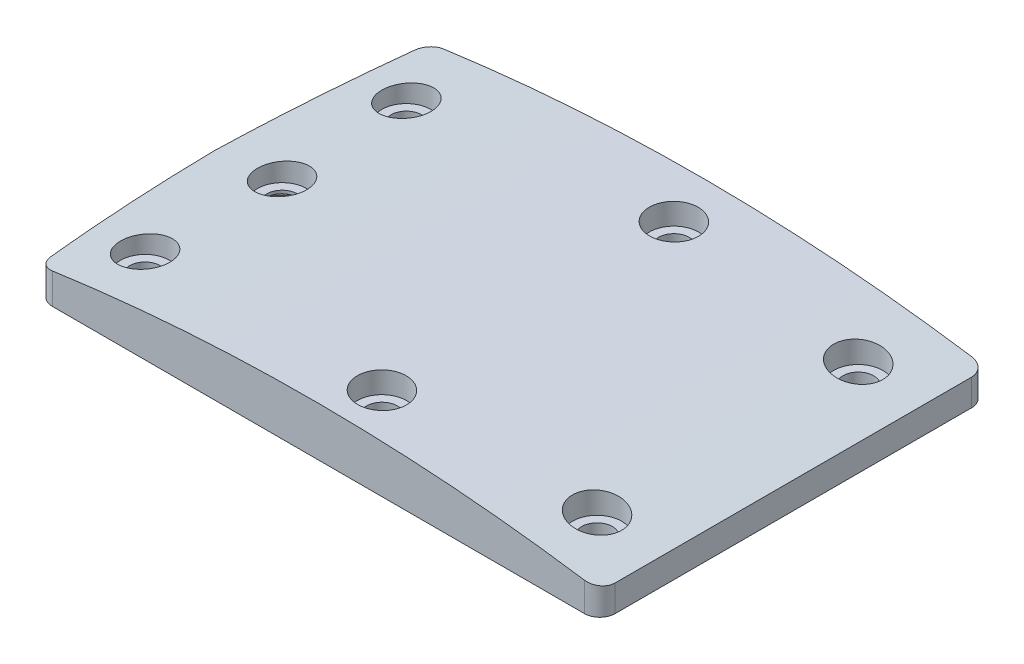
SolidWorks part; units mm, degrees
ref_plane "Front Plane" through (0, 0, 0) normal (0, 0, 1) x (1, 0, 0)
ref_plane "Top Plane" through (0, 0, 0) normal (0, 1, 0) x (1, 0, 0)
ref_plane "Right Plane" through (0, 0, 0) normal (1, 0, 0) x (0, 0, -1)
sketch "Sketch1" plane through (0, 0, 0) normal (0, 1, 0) x (1, 0, 0)
  line L1 (88.5752, 64.4067) -> (-83.4596, 64.4067)
  line L2 (93.5752, 59.4067) -> (93.5752, -56.5933)
  line L3 (88.5752, -61.5933) -> (-84.5844, -61.5933)
  line L5 (-76.4248, 0) -> (-76.3624, 0)
  line L13 (75.5752, -26.0764) -> (75.5752, 26.0764)
  line L14 (10.5752, 59.849) -> (10.5752, 49.4067) construction
  line L28 (-93.4248, 0) -> (-76.3624, 0)
  line L34 (147.9305, 0) -> (75.5752, 0) construction
  line L58 (28.2672, 49.4067) -> (54.5817, 49.4067)
  line L65 (75.5752, 48.9893) -> (75.5752, 49.4067)
  line L67 (75.5752, 64.4067) -> (75.5752, 77.8192)
  line L71 (10.5752, 44.4067) -> (10.5752, 38.9644) construction
  line L72 (-53.0672, 49.4067) -> (-6.3739, 49.4067)
  line L73 (-75.0534, 21.8192) -> (-75.0534, 17.3205)
  line L74 (10.5752, 44.4067) -> (10.5752, 38.9644) construction
  line L79 (-75.0534, -21.8192) -> (-75.0534, -17.3205)
  line L81 (-44.4248, 49.4067) -> (-44.4248, -49.4067)
  line L83 (-38.4248, 49.4067) -> (-38.4248, -49.4067)
  line L85 (-4.4248, -49.2149) -> (-4.4248, 49.2149)
  line L87 (1.5752, -45.474) -> (1.5752, 45.474)
  line L89 (35.5752, 49.4067) -> (35.5752, -49.4067)
  line L91 (41.5752, 49.4067) -> (41.5752, -49.4067)
  line L92 (-53.0672, -49.4067) -> (-6.3739, -49.4067)
  line L93 (28.2672, -49.4067) -> (54.5817, -49.4067)
  line L94 (-76.3624, 0) -> (-180.2852, 0) construction
  circle A0 centre (73.5752, 44.4067) radius 5
  circle A2 centre (-73.4248, 40.1495) radius 5
  circle A6 centre (10.5752, 49.4067) radius 5
  circle A27 centre (-71.4248, 0) radius 5
  arc A34 (-80.0534, 8.6603) -> (-80.0534, -8.6603) centre (-75.0534, 0) ccw
  arc A36 (-70.5181, 30.194) -> (-75.0534, 21.8192) centre (-65.0534, 21.8192) ccw
  arc A37 (-93.4248, 0) -> (-88.4151, 60.0719) centre (506.5049, -19.7858) cw
  arc A38 (-83.4596, 64.4067) -> (-88.4151, 60.0719) centre (-83.4596, 59.4067) ccw
  arc A39 (-93.4248, 0) -> (-89.5491, -57.1866) centre (465.7631, 9.1733) ccw
  arc A40 (-84.5844, -61.5933) -> (-89.5491, -57.1866) centre (-84.5844, -56.5933) cw
  arc A41 (88.5752, -61.5933) -> (93.5752, -56.5933) centre (88.5752, -56.5933) ccw
  arc A42 (93.5752, 59.4067) -> (88.5752, 64.4067) centre (88.5752, 59.4067) ccw
  arc A44 (-53.0672, 49.4067) -> (-63.0603, 39.7781) centre (-53.0672, 39.4067) ccw
  arc A45 (3.2464, 42.1362) -> (-6.3739, 49.4067) centre (-6.3739, 39.4067) ccw
  arc A46 (28.2672, 49.4067) -> (19.6069, 44.4067) centre (28.2672, 39.4067) ccw
  arc A47 (75.5752, 26.0764) -> (69.8802, 35.1023) centre (65.5752, 26.0764) ccw
  arc A49 (64.5609, 40.0516) -> (54.5817, 49.4067) centre (54.5817, 39.4067) ccw
  arc A50 (64.5609, 40.0516) -> (69.8802, 35.1023) centre (73.5752, 44.4067) ccw
  arc A51 (3.2464, 42.1362) -> (19.6069, 44.4067) centre (10.5752, 49.4067) ccw
  arc A52 (-70.5181, 30.194) -> (-63.0603, 39.7781) centre (-73.4248, 40.1495) ccw
  arc A53 (-80.0534, 8.6603) -> (-75.0534, 17.3205) centre (-85.0534, 17.3205) ccw
  circle A54 centre (73.5752, -44.4067) radius 5
  circle A55 centre (10.5752, -49.4067) radius 5
  circle A56 centre (-73.4248, -40.1495) radius 5
  arc A57 (-80.0534, -8.6603) -> (-80.0534, 8.6603) centre (-75.0534, 0) cw
  arc A58 (-80.0534, -8.6603) -> (-75.0534, -17.3205) centre (-85.0534, -17.3205) cw
  arc A59 (-70.5181, -30.194) -> (-75.0534, -21.8192) centre (-65.0534, -21.8192) cw
  arc A60 (-70.5181, -30.194) -> (-63.0603, -39.7781) centre (-73.4248, -40.1495) cw
  arc A61 (-53.0672, -49.4067) -> (-63.0603, -39.7781) centre (-53.0672, -39.4067) cw
  arc A62 (3.2464, -42.1362) -> (-6.3739, -49.4067) centre (-6.3739, -39.4067) cw
  arc A63 (3.2464, -42.1362) -> (19.6069, -44.4067) centre (10.5752, -49.4067) cw
  arc A64 (28.2672, -49.4067) -> (19.6069, -44.4067) centre (28.2672, -39.4067) cw
  arc A65 (64.5609, -40.0516) -> (54.5817, -49.4067) centre (54.5817, -39.4067) cw
  arc A66 (64.5609, -40.0516) -> (69.8802, -35.1023) centre (73.5752, -44.4067) cw
  arc A67 (75.5752, -26.0764) -> (69.8802, -35.1023) centre (65.5752, -26.0764) cw
  point P13 (-93.4248, 0)
  point P16 (0, 0)
  point P18 (0, 0)
  point P22 (0, 0)
  point P23 (0, 0)
  point P30 (0, 0)
  point P53 (93.5752, -61.5933)
  point P64 (93.5752, 64.4067)
  point P95 (41.5752, 0)
  point P96 (35.5752, 0)
  point P97 (1.5752, 0)
  point P98 (-4.4248, 0)
  point P99 (-38.4248, 0)
  point P100 (-44.4248, 0)
  dimension "D6" = 84
  dimension "D7" = 10
  dimension "D11" = 20
  dimension "D15" = 10
  dimension "D3" = 18
  dimension "10" = 10
  dimension "D26" = 22
  dimension "D29" = 187
  dimension "D16" = 10
  dimension "D2" = 126
  dimension "D4" = 65
  dimension "D9" = 15
  dimension "D18" = 20
sketch "Sketch4" plane through (0, 0, 0) normal (0, 1, 0) x (1, 0, 0)
  line L3 (88.5752, 64.4067) -> (-83.4596, 64.4067)
  line L4 (93.5752, -56.5933) -> (93.5752, 59.4067)
  line L5 (-84.5844, -61.5933) -> (88.5752, -61.5933)
  line L6 (88.5752, 64.4067) -> (-83.4596, 64.4067)
  line L7 (93.5752, -56.5933) -> (93.5752, 59.4067)
  line L8 (-84.5844, -61.5933) -> (88.5752, -61.5933)
  arc A14 (-88.4151, 60.0719) -> (-93.4248, 0) centre (506.5049, -19.7858) ccw
  arc A15 (-83.4596, 64.4067) -> (-88.4151, 60.0719) centre (-83.4596, 59.4067) ccw
  arc A16 (93.5752, 59.4067) -> (88.5752, 64.4067) centre (88.5752, 59.4067) ccw
  arc A17 (88.5752, -61.5933) -> (93.5752, -56.5933) centre (88.5752, -56.5933) ccw
  arc A18 (-89.5491, -57.1866) -> (-84.5844, -61.5933) centre (-84.5844, -56.5933) ccw
  arc A19 (-93.4248, 0) -> (-89.5491, -57.1866) centre (465.7631, 9.1733) ccw
  arc A20 (-88.4151, 60.0719) -> (-93.4248, 0) centre (506.5049, -19.7858) ccw
  arc A21 (-83.4596, 64.4067) -> (-88.4151, 60.0719) centre (-83.4596, 59.4067) ccw
  arc A22 (93.5752, 59.4067) -> (88.5752, 64.4067) centre (88.5752, 59.4067) ccw
  arc A23 (88.5752, -61.5933) -> (93.5752, -56.5933) centre (88.5752, -56.5933) ccw
  arc A24 (-89.5491, -57.1866) -> (-84.5844, -61.5933) centre (-84.5844, -56.5933) ccw
  arc A25 (-93.4248, 0) -> (-89.5491, -57.1866) centre (465.7631, 9.1733) ccw
  dimension "D5" = 0
extrude "Boss-Extrude1" add sketch "Sketch4" along normal blind 16
sketch "Sketch5" plane through (0, 0, 0) normal (0, 1, 0) x (1, 0, 0)
  line L0 (-93.4248, 0) -> (108.0865, 0) construction
  circle A0 centre (73.5752, -42.5) radius 5
  circle A1 centre (73.5752, 42.5) radius 5
  circle A3 centre (8.5752, -47.5) radius 5
  circle A5 centre (8.5752, 47.5) radius 5
  circle A7 centre (-73.4848, 42.515) radius 5
  circle A9 centre (-73.4848, -42.515) radius 5
  circle A11 centre (-71.4248, 0) radius 5
  dimension "D2" = 82.06
  dimension "D1" = 65
  dimension "D3" = 19.94
  dimension "D4" = 42.515
  dimension "D5" = 47.5
  dimension "D6" = 42.5
extrude "Cut-Extrude4" cut sketch "Sketch5" along normal through all from offset 16 offset against normal yes
sketch "Sketch7" plane through (0, 0, 0) normal (0, -1, 0) x (1, 0, 0)
  line L1 (-38.4248, 46.5933) -> (-5.7811, 46.5933)
  line L3 (24.9315, 46.5933) -> (35.5752, 46.5933)
  line L5 (41.5752, 46.5933) -> (56.1646, 46.5933)
  line L6 (75.5752, 26.5461) -> (75.5752, -26.5461)
  line L8 (-54.7435, 46.5933) -> (-44.4248, 46.5933)
  line L9 (-75.9293, 22.2) -> (-75.4248, 14.2829)
  line L12 (-44.4248, 46.5933) -> (-44.4248, -46.5933)
  line L14 (-38.4248, 46.5933) -> (-38.4248, -46.5933)
  line L16 (1.6129, 43.3959) -> (1.6129, -43.3259)
  line L18 (-4.4172, 46.62) -> (-4.4172, -46.5009)
  line L20 (41.5752, 46.5933) -> (41.5752, -46.5933)
  line L22 (35.5752, 46.5933) -> (35.5752, -46.5933)
  line L24 (41.5752, -46.5933) -> (56.1646, -46.5933)
  line L25 (24.9315, -46.5933) -> (35.5752, -46.5933)
  line L26 (-38.4248, -46.5933) -> (-5.7811, -46.5943)
  line L27 (-54.7435, -46.5933) -> (-44.4248, -46.5933)
  line L28 (-75.4248, -22.2889) -> (-75.4248, -14.2829)
  arc A0 (-69.7829, 33.2254) -> (-64.419, 38.2945) centre (-73.4848, 42.515) ccw
  arc A1 (-78.4248, 7.1414) -> (-78.4248, -7.1414) centre (-71.4248, 0) ccw
  arc A2 (1.8971, 43) -> (15.7241, 43.793) centre (8.5752, 47.5) ccw
  arc A4 (-54.7435, 46.5933) -> (-64.419, 38.2945) centre (-50.4409, 31.7872) ccw
  arc A5 (1.8971, 43) -> (1.6129, 43.3959) centre (-4.9383, 38.394) ccw
  arc A6 (24.9315, 46.5933) -> (15.7241, 43.793) centre (21.6953, 40.6967) ccw
  arc A7 (65.3699, 40.5) -> (56.1646, 46.5933) centre (56.1646, 36.5933) ccw
  arc A8 (75.5752, 26.5461) -> (69.8084, 34.941) centre (65.5981, 25.8706) ccw
  arc A9 (-69.7829, 33.2254) -> (-75.9293, 22.2) centre (-66.0811, 23.9358) ccw
  arc A10 (-78.4248, 7.1414) -> (-75.4248, 14.2829) centre (-85.4248, 14.2829) ccw
  arc A11 (65.3699, 40.5) -> (69.8084, 34.941) centre (73.5752, 42.5) ccw
  arc A12 (-4.4172, 46.62) -> (-5.7811, 46.5933) centre (-4.9383, 38.394) ccw
  arc A13 (65.3699, -40.5) -> (56.1646, -46.5933) centre (56.1646, -36.5933) cw
  arc A14 (65.3699, -40.5) -> (70.0752, -35.4764) centre (74.5752, -44.4067) cw
  arc A15 (75.5752, -26.5461) -> (70.0752, -35.4764) centre (65.5752, -26.5461) cw
  arc A16 (24.9315, -46.5933) -> (17.2534, -43) centre (24.9315, -36.5933) cw
  arc A17 (1.8971, -43) -> (17.2534, -43) centre (9.5752, -49.4067) cw
  arc A18 (1.8971, -43) -> (1.6129, -43.3259) centre (-5.7811, -36.5933) cw
  arc A19 (-4.4172, -46.5009) -> (-5.7811, -46.5943) centre (-5.7811, -36.5933) cw
  arc A20 (-54.7435, -46.5933) -> (-64.5841, -38.3714) centre (-54.7435, -36.5933) cw
  arc A21 (-69.9248, -31.2192) -> (-64.5841, -38.3714) centre (-74.4248, -40.1495) cw
  arc A22 (-69.9248, -31.2192) -> (-75.4248, -22.2889) centre (-65.4248, -22.2889) cw
  arc A23 (-78.4248, -7.1414) -> (-75.4248, -14.2829) centre (-85.4248, -14.2829) cw
extrude "Cut-Extrude5" cut sketch "Sketch7" against normal blind 4 contours L27 L12 L8 A4 A0 A9 L9 A10 A1 A23 L28 A22 A21 A20 | L20 L24 A13 A14 A15 L6 A8 A11 A7 L5 | L14 L26 A19 L18 A12 L1 | A16 A17 A18 L16 A5 A2 A6 L3 L22 L25
sketch "Sketch9" plane through (0, 0, 0) normal (0, -1, 0) x (1, 0, 0)
  line L20 (-38.4248, 46.5933) -> (-38.4248, -46.5933)
  line L21 (-5.7811, 46.5933) -> (-38.4248, 46.5933)
  line L22 (-4.4172, -46.5009) -> (-4.4172, 46.62)
  line L23 (-38.4248, -46.5933) -> (-5.7811, -46.5943)
  line L24 (-38.4248, 46.5933) -> (-38.4248, -46.5933)
  line L25 (-5.7811, 46.5933) -> (-38.4248, 46.5933)
  line L26 (-4.4172, -46.5009) -> (-4.4172, 46.62)
  line L27 (-38.4248, -46.5933) -> (-5.7811, -46.5943)
  arc A2 (-4.4172, 46.62) -> (-5.7811, 46.5933) centre (-4.9383, 38.394) ccw
  arc A3 (-5.7811, -46.5943) -> (-4.4172, -46.5009) centre (-5.7811, -36.5933) ccw
  arc A4 (-4.4172, 46.62) -> (-5.7811, 46.5933) centre (-4.9383, 38.394) ccw
  arc A5 (-5.7811, -46.5943) -> (-4.4172, -46.5009) centre (-5.7811, -36.5933) ccw
  dimension "D3" = 0
extrude "Cut-Extrude6" cut sketch "Sketch9" against normal blind 5 contours L24 L27 A5 L26 A4 L25
sketch "Sketch10" plane through (0, 0, 0) normal (0, -1, 0) x (1, 0, 0)
  line L4 (1.6129, 43.3959) -> (1.6129, -43.3259)
  line L5 (35.5752, 46.5933) -> (24.9315, 46.5933)
  line L6 (35.5752, -46.5933) -> (35.5752, 46.5933)
  line L7 (24.9315, -46.5933) -> (35.5752, -46.5933)
  line L8 (1.6129, 43.3959) -> (1.6129, -43.3259)
  line L9 (35.5752, 46.5933) -> (24.9315, 46.5933)
  line L10 (35.5752, -46.5933) -> (35.5752, 46.5933)
  line L11 (24.9315, -46.5933) -> (35.5752, -46.5933)
  arc A6 (1.8971, 43) -> (1.6129, 43.3959) centre (-4.9383, 38.394) ccw
  arc A7 (1.8971, 43) -> (15.7241, 43.793) centre (8.5752, 47.5) ccw
  arc A8 (24.9315, 46.5933) -> (15.7241, 43.793) centre (21.6953, 40.6967) ccw
  arc A9 (17.2534, -43) -> (24.9315, -46.5933) centre (24.9315, -36.5933) ccw
  arc A10 (17.2534, -43) -> (1.8971, -43) centre (9.5752, -49.4067) ccw
  arc A11 (1.6129, -43.3259) -> (1.8971, -43) centre (-5.7811, -36.5933) ccw
  arc A12 (1.8971, 43) -> (1.6129, 43.3959) centre (-4.9383, 38.394) ccw
  arc A13 (1.8971, 43) -> (15.7241, 43.793) centre (8.5752, 47.5) ccw
  arc A14 (24.9315, 46.5933) -> (15.7241, 43.793) centre (21.6953, 40.6967) ccw
  arc A15 (17.2534, -43) -> (24.9315, -46.5933) centre (24.9315, -36.5933) ccw
  arc A16 (17.2534, -43) -> (1.8971, -43) centre (9.5752, -49.4067) ccw
  arc A17 (1.6129, -43.3259) -> (1.8971, -43) centre (-5.7811, -36.5933) ccw
  dimension "D1" = 0
extrude "Cut-Extrude7" cut sketch "Sketch10" against normal blind 5 contours L8 A17 A16 A15 L11 L10 L9 A14 A13 A12
sketch "Sketch11" plane through (0, 0, 61.5933) normal (0, 0, 1) x (1, 0, 0)
  line L1 (-103.3641, 16) -> (102.9431, 16)
  line L3 (-103.3641, 16) -> (-103.3641, 7.0295)
  line L4 (102.9431, 16) -> (102.9431, 7.103)
  arc A0 (102.9431, 7.103) -> (-103.3641, 7.0295) centre (0, -584) ccw
  line M4 (88.5752, 0) -> (88.5752, 16)
  line M5 (88.5752, 16) -> (-84.5844, 16)
  line M6 (-84.5844, 16) -> (-84.5844, 0)
extrude "Cut-Extrude8" cut sketch "Sketch11" against normal through all contours A0 L1 L3 M6 | A0 L1 M6 | A0 L4 L1 M4 | A0 M4 M5 region at (66.4557, 14.0297, 61.5933) region at (-94.6016, 12.235, 61.5933) region at (-63.4595, 14.2039, 61.5933) region at (96.1201, 12.118, 61.5933)
fillet "Fillet1" radius 3 10 edges at (-44.4248, 2, 46.5933) (41.5752, 2, 46.5933) (35.5752, 2.5, 46.5933) (-4.4172, 2.5, 46.62) (-38.4248, 2.5, 46.5933) (-38.4248, 2.5, -46.5933) (41.5752, 2, -46.5933) (35.5752, 2.5, -46.5933) (-4.4172, 2.5, -46.5009) (-44.4248, 2, -46.5933)
sketch "Sketch12" plane through (0, 0, 0) normal (0, -1, 0) x (1, 0, 0)
  line L0 (-108.1748, 0) -> (-79.4248, 0) construction
  line L1 (-63.4248, 0) -> (102.8384, 0) construction
  circle A0 centre (-73.4848, 42.515) radius 8
  circle A1 centre (8.5752, 47.5) radius 8
  circle A2 centre (73.5752, 42.5) radius 8
  circle A3 centre (-71.4248, 0) radius 8
  circle A4 centre (73.5752, -42.5) radius 8
  circle A5 centre (8.5752, -47.5) radius 8
  circle A6 centre (-73.4848, -42.515) radius 8
sketch "Sketch13" plane through (0, 0, 0) normal (0, 1, 0) x (1, 0, 0)
  circle A0 centre (-73.4848, -42.515) radius 8 construction
  circle A1 centre (-73.4848, 42.515) radius 8 construction
  circle A2 centre (-73.4848, -42.515) radius 8
  circle A3 centre (-73.4848, 42.515) radius 8
  circle A4 centre (-71.4248, 0) radius 8 construction
  circle A5 centre (-71.4248, 0) radius 8
  circle A6 centre (73.5752, 42.5) radius 8 construction
  circle A7 centre (73.5752, -42.5) radius 8 construction
  circle A8 centre (73.5752, 42.5) radius 8
  circle A9 centre (73.5752, -42.5) radius 8
extrude "Cut-Extrude10" cut sketch "Sketch13" along normal through all from offset 5
extrude "Cut-Extrude11" cut sketch "Sketch12" against normal through all from offset 9 contours A1 | A5 region at (8.5752, 0, 47.5) region at (8.5752, 0, -47.5) offset against normal yes
